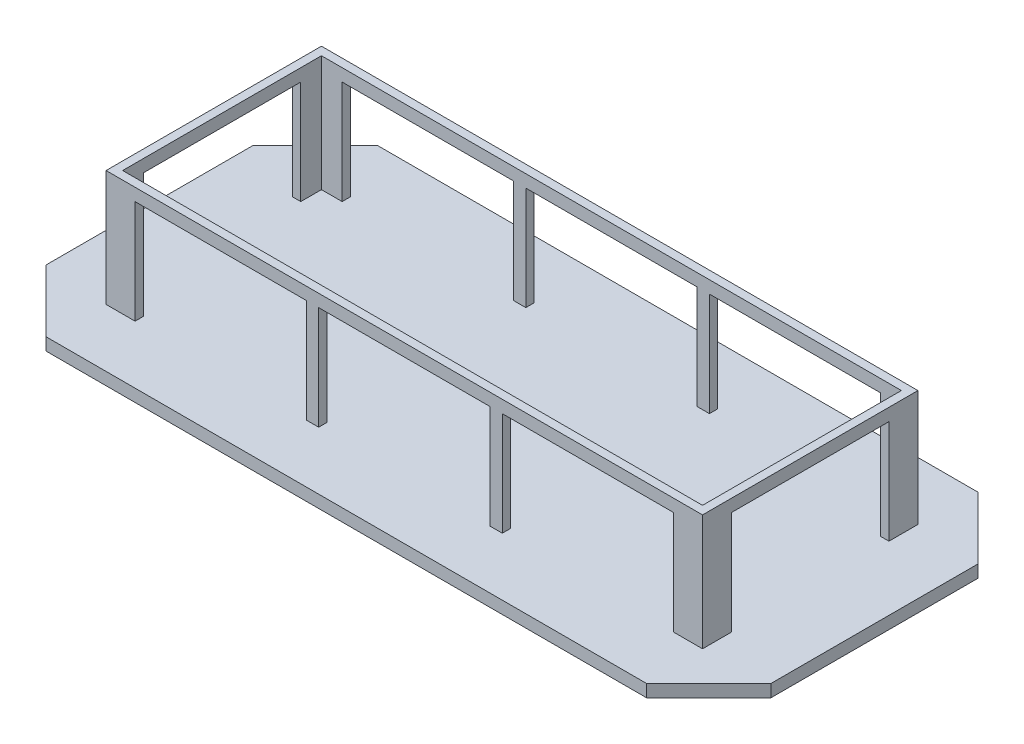
SolidWorks part; units mm, degrees
ref_plane "Спереди" through (0, 0, 0) normal (0, 0, 1) x (1, 0, 0)
ref_plane "Сверху" through (0, 0, 0) normal (0, 1, 0) x (1, 0, 0)
ref_plane "Справа" through (0, 0, 0) normal (1, 0, 0) x (0, 0, -1)
sketch "Эскиз1" plane through (0, 0, 0) normal (0, 1, 0) x (1, 0, 0)
  line L0 (-87.5, 25) -> (-72.5, 40)
  line L1 (-72.5, -40) -> (72.5, -40)
  line L2 (-87.5, -25) -> (-87.5, 25)
  line L3 (-72.5, 40) -> (72.5, 40)
  line L4 (87.5, -25) -> (87.5, 25)
  line L5 (-87.5, -40) -> (87.5, 40) construction
  line L6 (-87.5, 40) -> (87.5, -40) construction
  line L7 (-87.5, -25) -> (-72.5, -40)
  line L8 (72.5, -40) -> (87.5, -25)
  line L9 (72.5, 40) -> (87.5, 25)
  point P0 (0, 0)
  dimension "D1" = 175
  dimension "D2" = 80
extrude "Бобышка-Вытянуть1" add sketch "Эскиз1" along normal blind 3
sketch "Эскиз2" plane through (0, 3, 0) normal (0, 1, 0) x (1, 0, 0)
  line L1 (-70, 24) -> (70, 24)
  line L2 (-70, 24) -> (-70, -24)
  line L3 (-70, -24) -> (70, -24)
  line L4 (70, 24) -> (70, -24)
  line L5 (-70, 24) -> (70, -24) construction
  line L6 (-70, -24) -> (70, 24) construction
  line L7 (-72, 26) -> (72, 26)
  line L8 (-72, 26) -> (-72, -26)
  line L9 (-72, -26) -> (72, -26)
  line L10 (72, 26) -> (72, -26)
  line L11 (-72, 26) -> (72, -26) construction
  line L12 (-72, -26) -> (72, 26) construction
  point P0 (0, 0)
  point P6 (0, 0)
  dimension "D1" = 144
  dimension "D2" = 52
  dimension "D3" = 48
  dimension "D4" = 140
extrude "Бобышка-Вытянуть2" add sketch "Эскиз2" along normal blind 28
sketch "Эскиз3" plane through (0, 0, 26) normal (0, 0, 1) x (1, 0, 0)
  line L0 (-72.5, 3) -> (72.5, 3) construction
  line L1 (-65, 28) -> (-23.6667, 28)
  line L2 (-65, 28) -> (-65, 3)
  line L3 (-65, 3) -> (-23.6667, 3)
  line L4 (-23.6667, 28) -> (-23.6667, 3)
  line L5 (-72, 31) -> (-72, 3) construction
  line L6 (-72, 31) -> (72, 31) construction
  line L7 (-20.67, 28) -> (-20.67, 3)
  line L8 (-20.67, 28) -> (20.6633, 28)
  line L9 (20.6633, 28) -> (20.6633, 3)
  line L10 (-20.67, 3) -> (20.6633, 3)
  line L11 (23.66, 28) -> (23.66, 3)
  line L12 (23.66, 28) -> (64.9933, 28)
  line L13 (64.9933, 28) -> (64.9933, 3)
  line L14 (23.66, 3) -> (64.9933, 3)
  dimension "D1" = 7
  dimension "D2" = 3
  dimension "D3" = 41.3333
  dimension "D4" = 3
extrude "Вырез-Вытянуть1" cut sketch "Эскиз3" against normal up to surface (52 mm away) up to face at (0, 17, -26)
sketch "Эскиз4" plane through (-72, 0, 0) normal (-1, 0, 0) x (0, 0, 1)
  line L0 (-25, 3) -> (25, 3) construction
  line L1 (-19, 28) -> (19, 28)
  line L2 (-19, 28) -> (-19, 3)
  line L3 (-19, 3) -> (19, 3)
  line L4 (19, 28) -> (19, 3)
  line L5 (-26, 31) -> (-26, 3) construction
  line L6 (26, 31) -> (26, 3) construction
  line L7 (-26, 31) -> (26, 31) construction
  dimension "D1" = 7
  dimension "D2" = 7
  dimension "D3" = 3
extrude "Вырез-Вытянуть2" cut sketch "Эскиз4" against normal up to surface (144 mm away) up to face at (72, 17, 0)
